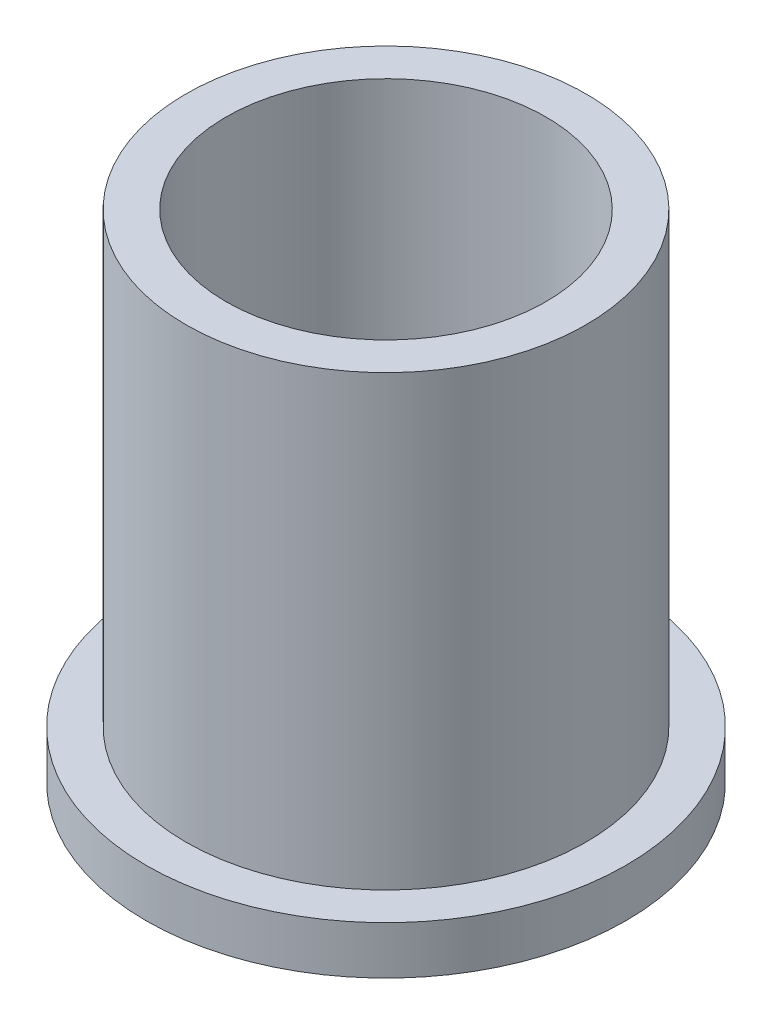
SolidWorks part; units mm, degrees
material "Brass"
ref_plane "Front Plane" through (0, 0, 0) normal (0, 0, 1) x (1, 0, 0)
ref_plane "Top Plane" through (0, 0, 0) normal (0, 1, 0) x (1, 0, 0)
ref_plane "Right Plane" through (0, 0, 0) normal (1, 0, 0) x (0, 0, -1)
sketch "Sketch1" plane through (0, 0, 0) normal (0, 1, 0) x (1, 0, 0)
  circle A0 centre (0, 0) radius 15
  circle A1 centre (0, 0) radius 10
  circle A2 centre (0, 0) radius 12.5
  dimension "D1" = 30
  dimension "D2" = 20
  dimension "D3" = 25
extrude "Boss-Extrude1" add sketch "Sketch1" along normal blind 3 contours A0
extrude "Boss-Extrude2" add sketch "Sketch1<3>" along normal blind 31 contours A2
sketch "Sketch1<3>" plane through (0, 0, 0) normal (0, 1, 0) x (1, 0, 0) same geometry as "Sketch1"
extrude "Cut-Extrude1" cut sketch "Sketch1<4>" along normal through all both and the other way through all contours A1
sketch "Sketch1<4>" plane through (0, 0, 0) normal (0, 1, 0) x (1, 0, 0) same geometry as "Sketch1"
